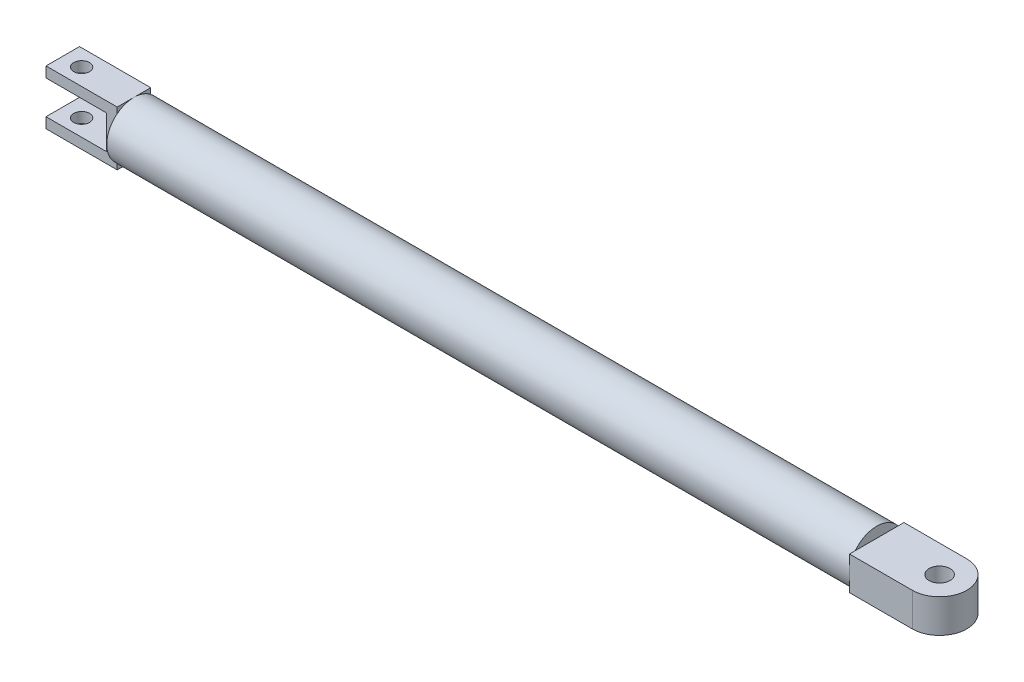
SolidWorks part; units mm, degrees
ref_plane "Front Plane" through (0, 0, 0) normal (0, 0, 1) x (1, 0, 0)
ref_plane "Top Plane" through (0, 0, 0) normal (0, 1, 0) x (1, 0, 0)
ref_plane "Right Plane" through (0, 0, 0) normal (1, 0, 0) x (0, 0, -1)
sketch "Sketch1" plane through (0, 0, 0) normal (1, 0, 0) x (0, 0, -1)
  circle A0 centre (0, 0) radius 8.255
  dimension "D1" = 16.51
extrude "Boss-Extrude1" add sketch "Sketch1" along normal blind 225.171
sketch "Sketch2" plane through (0, 0, 0) normal (0, 1, 0) x (1, 0, 0)
  line L0 (225.171, -8.255) -> (225.171, 8.255) construction
  line L1 (225.171, -8.255) -> (225.171, 8.255)
  line L2 (225.171, 8.255) -> (244.221, 8.255)
  line L3 (225.171, -8.255) -> (244.221, -8.255)
  arc A0 (244.221, 8.255) -> (244.221, -8.255) centre (244.221, 0) cw
  circle A1 centre (244.221, 0) radius 3.175
  dimension "D2" = 6.35
  dimension "D1" = 19.05
extrude "Boss-Extrude2" add sketch "Sketch2" along normal blind 5.08 and the other way blind 5.08
sketch "Sketch3" plane through (0, 0, 0) normal (0, 0, 1) x (1, 0, 0)
  line L0 (225.171, 8.255) -> (0, 8.255) construction
  line L1 (0, 8.255) -> (-21.59, 8.255)
  line L2 (0, 8.255) -> (0, -8.255)
  line L3 (0, -8.255) -> (-21.59, -8.255)
  line L4 (-21.59, 8.255) -> (-21.59, -8.255)
  line L5 (0, -8.255) -> (225.171, -8.255) construction
  line L7 (-3.175, 5.08) -> (-21.59, 5.08)
  line L8 (-3.175, 5.08) -> (-3.175, -5.08)
  line L9 (-3.175, -5.08) -> (-21.59, -5.08)
  line L10 (-21.59, 5.08) -> (-21.59, -5.08)
  point P13 (-21.59, 0)
  point P14 (-21.59, 0)
  dimension "D1" = 21.59
  dimension "D2" = 3.175
  dimension "D3" = 3.175
extrude "Boss-Extrude3" add sketch "Sketch3" along normal blind 5.08 and the other way blind 5.08 contours L8 L9 L4 L3 L2 L1 L7 region at (-0.2718, 0, 0)
sketch "Sketch4" plane through (0, -5.08, 0) normal (0, 1, 0) x (1, 0, 0)
  line L0 (0, 5.08) -> (0, 0) construction
  line L1 (0, 5.08) -> (0, 0)
  circle A0 centre (-15.875, 0) radius 2.3983
  dimension "D1" = 15.875
extrude "Cut-Extrude1" cut sketch "Sketch4" against normal through all both and the other way through all contours A0 region at (-15.875, -5.08, 0)
sketch3d "3DSketch1"
  line L0 (-15.875, 8.255, 0) -> (-15.875, -8.255, 0)
  circle A0 centre (-15.875, -8.255, 0) radius 2.3983 construction
  circle A1 centre (-15.875, -8.255, 0) radius 2.3983
  circle A2 centre (-15.875, 8.255, 0) radius 2.3983 construction
  circle A3 centre (-15.875, 8.255, 0) radius 2.3983
  point P2 (-15.875, -5.8567, 0)
  point P4 (-15.875, -5.8567, 0)
  point P7 (-15.875, 10.6533, 0)
  point P9 (-15.875, 10.6533, 0)
  point P10 (-15.875, 0, 0)
ref_point "Point1"
ref_point "Point2"
